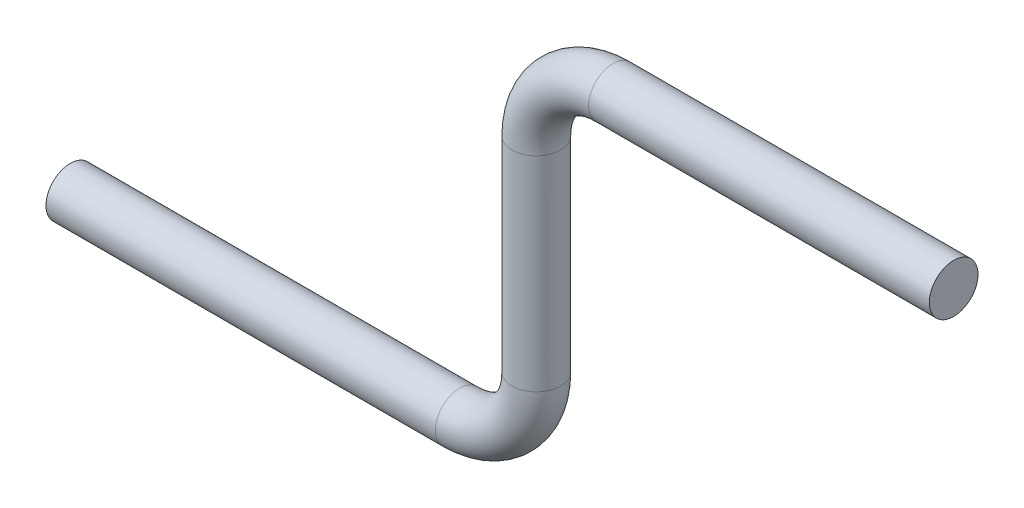
SolidWorks part; units mm, degrees
ref_plane "Front" through (0, 0, 0) normal (0, 0, 1) x (1, 0, 0)
ref_plane "Top" through (0, 0, 0) normal (0, 1, 0) x (1, 0, 0)
ref_plane "Right" through (0, 0, 0) normal (1, 0, 0) x (0, 0, -1)
sketch "Sketch1" plane through (0, 0, 0) normal (0, 0, 1) x (1, 0, 0)
  line L0 (-15.5632, 0) -> (24.4368, 0)
  line L1 (55, 0) -> (-55, 0) construction
  line L2 (32.3103, 7.8735) -> (32.3103, 28.8735)
  line L3 (40.1838, 36.747) -> (75.1838, 36.747)
  arc A0 (24.4368, 0) -> (32.3103, 7.8735) centre (24.4368, 7.8735) ccw
  arc A1 (40.1838, 36.747) -> (32.3103, 28.8735) centre (40.1838, 28.8735) ccw
  point P8 (24.4368, 0)
  point P12 (32.3103, 28.8735)
  dimension "D3" = 15.747
  dimension "D4" = 15.747
  dimension "D1" = 40
  dimension "D2" = 35
  dimension "D5" = 21
ref_plane "Plane1" through (-15.5632, 0, 0) normal (1, 0, 0) x (0, 0, -1)
sketch "Sketch3" plane through (-15.5632, 0, 0) normal (1, 0, 0) x (0, 0, -1)
  circle A0 centre (0, 0) radius 2.5
  point P0 (0, 0)
sweep "Sweep1" add profiles "Sketch3" path "Sketch1"
